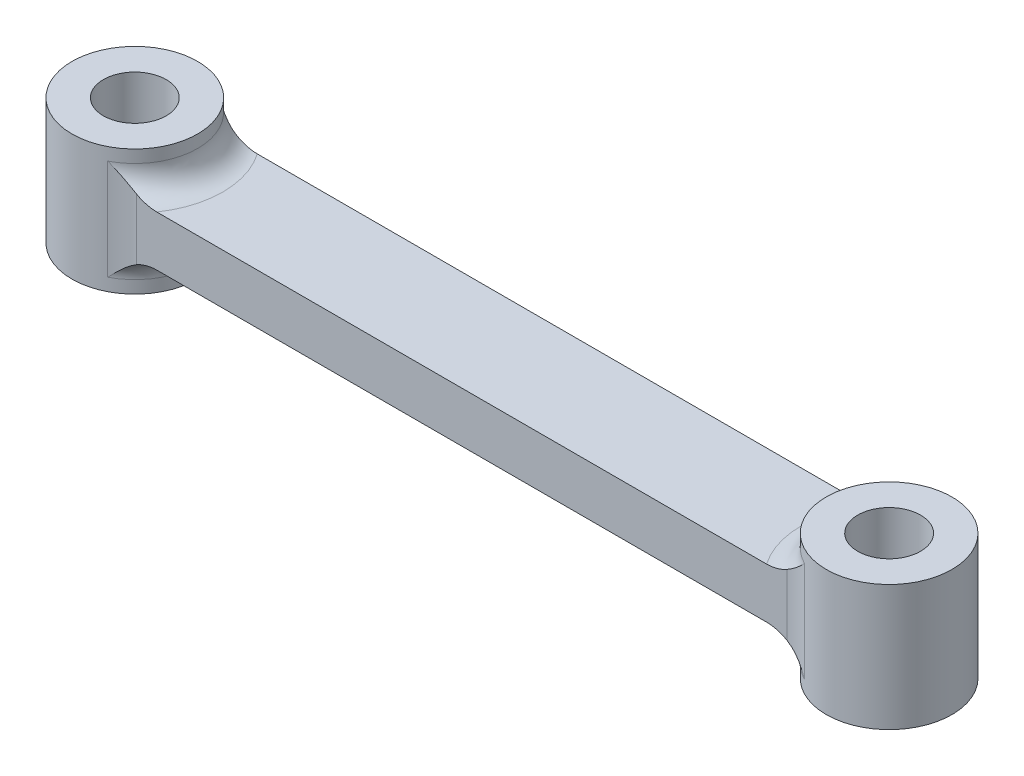
SolidWorks part; units mm, degrees
ref_plane "Front Plane" through (0, 0, 0) normal (0, 0, 1) x (1, 0, 0)
ref_plane "Top Plane" through (0, 0, 0) normal (0, 1, 0) x (1, 0, 0)
ref_plane "Right Plane" through (0, 0, 0) normal (1, 0, 0) x (0, 0, -1)
sketch "Sketch1" plane through (0, 0, 0) normal (0, 1, 0) x (1, 0, 0)
  line L0 (-30, -4) -> (-30, -5) construction
  line L2 (30, 5) -> (30, -5) construction
  line L4 (-30, 5) -> (-30, 4) construction
  line L5 (30, 5) -> (-30, -5) construction
  line L6 (30, -5) -> (-30, 5) construction
  line L7 (25.8769, -4) -> (-25.8769, -4)
  line L8 (30, -4) -> (30, 4)
  line L9 (25.8769, 4) -> (-25.8769, 4)
  line L11 (30, -4) -> (-30, 4) construction
  line L12 (0, 0) -> (-26.4565, -3.5275) construction
  arc A0 (-27.7094, 4.4444) -> (-27.7094, -4.4444) centre (-30, 0) ccw
  arc A1 (27.7094, -4.4444) -> (27.7094, 4.4444) centre (30, 0) ccw
  circle A2 centre (30, 0) radius 2.5
  circle A3 centre (-30, 0) radius 2.5
  arc A4 (-25.8769, -4) -> (-27.7094, -4.4444) centre (-25.8769, -8) ccw
  arc A5 (-25.8769, 4) -> (-27.7094, 4.4444) centre (-25.8769, 8) cw
  arc A6 (27.7094, -4.4444) -> (25.8769, -4) centre (25.8769, -8) ccw
  arc A7 (25.8769, 4) -> (27.7094, 4.4444) centre (25.8769, 8) ccw
  point P4 (0, 0)
  point P14 (0, 0)
  dimension "D1" = 10
  dimension "D2" = 10
  dimension "D5" = 5
  dimension "D6" = 5
  dimension "D8" = 4
  dimension "D3" = 60
  dimension "D4" = 30
  dimension "D7" = 8
extrude "Boss-Extrude1" add sketch "Sketch1" along normal mid plane 4 contours A7 L9 A5 A0 A4 L7 A6 A1 A3 A2 region at (0, 0, 0)
sketch "Sketch3" plane through (0, 0, 0) normal (0, 1, 0) x (1, 0, 0)
  arc A1 (-27.7094, 4.4444) -> (-27.7094, -4.4444) centre (-30, 0) ccw construction
  circle A2 centre (-30, 0) radius 5
  arc A3 (27.7094, -4.4444) -> (27.7094, 4.4444) centre (30, 0) ccw construction
  circle A4 centre (30, 0) radius 5
  circle A5 centre (30, 0) radius 2.5 construction
  circle A6 centre (30, 0) radius 2.5
  circle A7 centre (-30, 0) radius 2.5 construction
  circle A8 centre (-30, 0) radius 2.5
  point P3 (-25.8769, -8)
  point P8 (27.1901, 4.4444)
extrude "Boss-Extrude2" add sketch "Sketch3" along normal mid plane 10
fillet "Fillet1" radius 2 4 edges at (25, 2, 0) (25, -2, 0) (-25, 2, 0) (-25, -2, 0)
